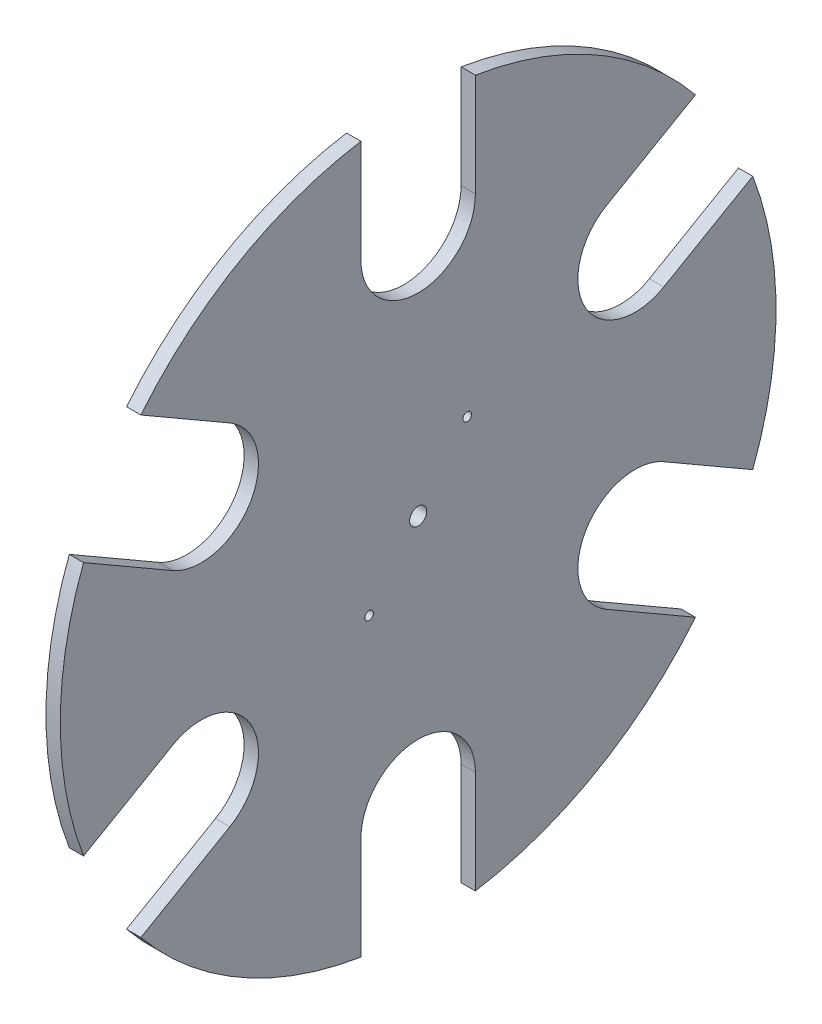
SolidWorks part; units mm, degrees
material "1060-H12"
ref_plane "Front Plane" through (0, 0, 0) normal (0, 0, 1) x (1, 0, 0)
ref_plane "Top Plane" through (0, 0, 0) normal (0, 1, 0) x (1, 0, 0)
ref_plane "Right Plane" through (0, 0, 0) normal (1, 0, 0) x (0, 0, -1)
sketch "Sketch1" plane through (0, 0, 0) normal (1, 0, 0) x (0, 0, -1)
  line L0 (0, 0) -> (0, 250) construction
  line L1 (0, 0) -> (216.5064, 125) construction
  line L2 (0, 0) -> (216.5064, -125) construction
  line L3 (0, 0) -> (0, -250) construction
  line L4 (0, 0) -> (-216.5064, -125) construction
  line L5 (0, 0) -> (-216.5064, 125) construction
  circle A0 centre (0, 0) radius 250
  circle A1 centre (0, 0) radius 6
  circle A2 centre (0, 175) radius 40
  circle A3 centre (151.5544, 87.5) radius 40
  circle A4 centre (151.5544, -87.5) radius 40
  circle A5 centre (0, -175) radius 40
  circle A6 centre (-151.5544, -87.5) radius 40
  circle A7 centre (-151.5544, 87.5) radius 40
  point P13 (0, 0)
  point P26 (0, 0)
  dimension "D1" = 500
  dimension "D2" = 12
  dimension "D4" = 80
  dimension "D5" = 175
  dimension "D3" = 6
  dimension "D6" = 6
extrude "Boss-Extrude1" add sketch "Sketch1" along normal blind 10
ref_plane "Plane1" through (10, 0, 0) normal (-1, 0, 0) x (0, 0, 1)
sketch "Sketch2" plane through (0, 0, 0) normal (-1, 0, 0) x (0, 0, 1)
  line L0 (-40, 175) -> (-40, 246.7793)
  line L1 (40, 175) -> (40, 246.7793)
  line L2 (131.5544, 122.141) -> (193.7171, 158.0306)
  line L3 (171.5544, 52.859) -> (233.7171, 88.7486)
  line L4 (171.5544, -52.859) -> (233.7171, -88.7486)
  line L5 (131.5544, -122.141) -> (193.7171, -158.0306)
  line L6 (40, -175) -> (40, -246.7793)
  line L7 (-40, -175) -> (-40, -246.7793)
  line L8 (-131.5544, -122.141) -> (-193.7171, -158.0306)
  line L9 (-171.5544, -52.859) -> (-233.7171, -88.7486)
  line L10 (-171.5544, 52.859) -> (-233.7171, 88.7486)
  line L11 (-131.5544, 122.141) -> (-193.7171, 158.0306)
  circle A0 centre (0, 175) radius 40 construction
  circle A1 centre (0, 0) radius 250 construction
  arc A2 (-40, 175) -> (40, 175) centre (0, 175) cw
  arc A3 (-40, 246.7793) -> (40, 246.7793) centre (0, 0) cw
  arc A4 (131.5544, 122.141) -> (171.5544, 52.859) centre (151.5544, 87.5) cw
  arc A5 (193.7171, 158.0306) -> (233.7171, 88.7486) centre (0, 0) cw
  arc A6 (171.5544, -52.859) -> (131.5544, -122.141) centre (151.5544, -87.5) cw
  arc A7 (233.7171, -88.7486) -> (193.7171, -158.0306) centre (0, 0) cw
  arc A8 (40, -175) -> (-40, -175) centre (0, -175) cw
  arc A9 (40, -246.7793) -> (-40, -246.7793) centre (0, 0) cw
  arc A10 (-131.5544, -122.141) -> (-171.5544, -52.859) centre (-151.5544, -87.5) cw
  arc A11 (-193.7171, -158.0306) -> (-233.7171, -88.7486) centre (0, 0) cw
  arc A12 (-171.5544, 52.859) -> (-131.5544, 122.141) centre (-151.5544, 87.5) cw
  arc A13 (-233.7171, 88.7486) -> (-193.7171, 158.0306) centre (0, 0) cw
  circle A14 centre (-34.2487, 43.0352) radius 3
  circle A15 centre (34.2487, -43.0352) radius 3
  point P52 (0, 0)
  dimension "D1" = 6
extrude "Cut-Extrude1" cut sketch "Sketch2" against normal through all both and the other way through all
